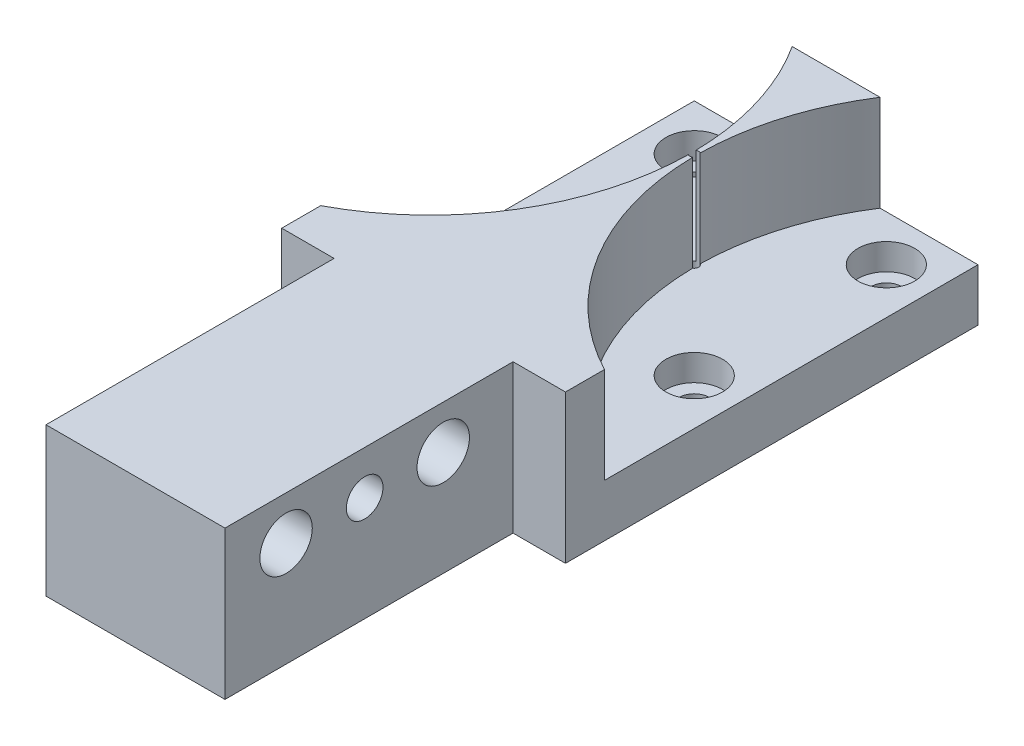
SolidWorks part; units mm, degrees
ref_plane "Front Plane" through (0, 0, 0) normal (0, 0, 1) x (1, 0, 0)
ref_plane "Top Plane" through (0, 0, 0) normal (0, 1, 0) x (1, 0, 0)
ref_plane "Right Plane" through (0, 0, 0) normal (1, 0, 0) x (0, 0, -1)
sketch "Sketch1" plane through (0, 0, 0) normal (0, 1, 0) x (1, 0, 0)
  line L0 (-16.25, 0) -> (16.25, 0)
  line L1 (-16.25, 0) -> (-16.25, -80.25)
  line L2 (-16.25, -80.25) -> (16.25, -80.25)
  line L3 (16.25, -80.25) -> (16.25, 0)
  line L4 (-0.45, -16.25) -> (-0.25, -16.25) construction
  line L5 (0.45, -16.25) -> (0.25, -16.25) construction
  line L6 (-16.25, -52.25) -> (16.25, -52.25) construction
  line L7 (11, -27.25) -> (-11, -27.25) construction
  line L8 (11, -27.25) -> (11, -5.25) construction
  line L9 (11, -5.25) -> (-11, -5.25) construction
  line L10 (-11, -27.25) -> (-11, -5.25) construction
  line L11 (11, -27.25) -> (-11, -5.25) construction
  line L12 (11, -5.25) -> (-11, -27.25) construction
  line L13 (-16.25, -58.25) -> (16.25, -58.25) construction
  line L14 (-16.25, -76.25) -> (16.25, -76.25) construction
  line L15 (-16.25, -70.25) -> (16.25, -70.25) construction
  line L16 (-16.25, -66.75) -> (16.25, -66.75) construction
  line L17 (-16.25, -61.75) -> (16.25, -61.75) construction
  line L18 (0, -52.25) -> (0, -58.25) construction
  line L19 (0, -66.75) -> (0, -61.75) construction
  line L20 (0, -70.25) -> (0, -76.25) construction
  line L21 (0, -58.25) -> (0, -66.75) construction
  line L22 (0, -61.75) -> (0, -70.25) construction
  line L23 (-16.25, -48.25) -> (16.25, -48.25) construction
  line L24 (0, -52.25) -> (0, -48.25) construction
  line L25 (0, -76.25) -> (0, -80.25) construction
  line L26 (0, -16.25) -> (0, 15.25) construction
  line L27 (-12.775, 15.25) -> (12.775, 15.25) construction
  line L28 (-30.25, -46.25) -> (-30.25, -48.25) construction
  arc A0 (-16.25, -42.783) -> (-5.0322, 0) centre (-30.25, -16.25) ccw construction
  circle A1 centre (0, -16.25) radius 0.45 construction
  arc A2 (5.0322, 0) -> (16.25, -42.783) centre (30.25, -16.25) ccw construction
  circle A3 centre (-11, -5.25) radius 5.25 construction
  circle A4 centre (-11, -5.25) radius 3.25 construction
  circle A5 centre (-11, -5.25) radius 1.5 construction
  arc A6 (-16.25, -42.783) -> (-5.0322, 0) centre (-30.25, -16.25) cw construction
  circle A7 centre (-12.775, 15.25) radius 5 construction
  circle A8 centre (12.775, 15.25) radius 5 construction
  point P43 (0, -55.25)
  point P44 (0, -73.25)
  dimension "D1" = 0.9
  dimension "D4" = 2
  dimension "D5" = 6.5
  dimension "D6" = 3
  dimension "D7" = 30
  dimension "D17" = 10
  dimension "D2" = 0.2
  dimension "D3" = 22
  dimension "D8" = 32.5
  dimension "D9" = 4
  dimension "D10" = 6
  dimension "D11" = 18
  dimension "D12" = 5
  dimension "D13" = 2
  dimension "D15" = 31.5
  dimension "D16" = 25.55
  dimension "D18" = 3.5
extrude "Boss-Extrude1" add sketch "Sketch1" against normal blind 6
sketch "Sketch2" plane through (0, 0, 0) normal (0, 1, 0) x (1, 0, 0)
  line L0 (-5.0322, 0) -> (5.0322, 0)
  line L1 (-16.25, -42.783) -> (-16.25, -80.25)
  line L2 (-16.25, -80.25) -> (16.25, -80.25)
  line L3 (16.25, -80.25) -> (16.25, -42.783)
  arc A0 (5.0322, 0) -> (16.25, -42.783) centre (30.25, -16.25) ccw construction
  arc A1 (-16.25, -42.783) -> (-5.0322, 0) centre (-30.25, -16.25) ccw construction
  arc A2 (5.0322, 0) -> (16.25, -42.783) centre (30.25, -16.25) ccw
  arc A3 (-16.25, -42.783) -> (-5.0322, 0) centre (-30.25, -16.25) ccw
extrude "Boss-Extrude2" add sketch "Sketch2" along normal blind 11
sketch "Sketch3" plane through (16.25, 0, 0) normal (1, 0, 0) x (0, 0, -1)
  line L0 (-73.25, 11) -> (-73.25, 1) construction
  line L1 (-80.25, 11) -> (-42.783, 11) construction
  line L3 (-55.25, 11) -> (-55.25, 1) construction
  line L4 (-64.25, 11) -> (-64.25, 1) construction
  line L6 (-80.25, 0) -> (0, 0) construction
  line L7 (-66.75, 0) -> (-61.75, 0) construction
  point P20 (-64.25, 0)
  dimension "D1" = 10
hole_wizard "Ø6.0mm Dowel Hole1" positions "Sketch4" profile "Sketch5" hole size "Ø6.0" standard "ANSI Metric" end condition through all
sketch "Sketch4" plane through (16.25, 0, 0) normal (1, 0, 0) x (0, 0, -1)
  line L0 (-73.25, 11) -> (-73.25, 1) construction
  line L1 (-55.25, 11) -> (-55.25, 1) construction
  point P0 (-73.25, 6)
  point P4 (-55.25, 6)
sketch "Sketch5" plane through (16.25, 6, 73.25) normal (0, 1, 0) x (0, 0, -1)
  line L0 (0, 0) -> (0, 32.5)
  line L1 (0, 32.5) -> (3, 32.5)
  line L2 (3, 32.5) -> (3, 0)
  line L5 (3, 0) -> (0, 0)
  line L11 (0, -6.35) -> (0, 107.95) construction
  dimension "Thru Hole Dia." = 6
  dimension "Thru Hole Depth" = 32.5
hole_wizard "M5x0.8 Tapped Hole1" positions "Sketch6" profile "Sketch7" tap size "M5x0.8" standard "ANSI Metric" end condition through all
sketch "Sketch6" plane through (16.25, 0, 0) normal (1, 0, 0) x (0, 0, -1)
  line L0 (-64.25, 11) -> (-64.25, 1) construction
  point P0 (-64.25, 6)
sketch "Sketch7" plane through (16.25, 6, 64.25) normal (0, 1, 0) x (0, 0, -1)
  line L0 (0, 0) -> (0, 32.5)
  line L1 (0, 32.5) -> (2.1, 32.5)
  line L2 (2.1, 32.5) -> (2.1, 0)
  line L5 (2.1, 0) -> (0, 0)
  line L11 (0, -6.35) -> (0, 107.95) construction
  dimension "Thru Tap Drill Dia." = 4.2
  dimension "Thru Tap Drill Depth" = 32.5
cosmetic thread "Hole Thread1" parameters "D2"=5
hole_wizard "CBORE for M3 SHCS1" positions "Sketch8" profile "Sketch9" counterbore size "M3" standard "ANSI Metric" end condition through all
sketch "Sketch8" plane through (0, 0, 0) normal (0, 1, 0) x (1, 0, 0)
  point P0 (-11, -5.25)
  point P3 (11, -5.25)
  point P6 (11, -27.25)
  point P9 (-11, -27.25)
sketch "Sketch9" plane through (-11, 0, 5.25) normal (1, 0, 0) x (0, 0, 1)
  line L0 (0, 0) -> (0, 6)
  line L1 (0, 6) -> (1.7, 6)
  line L3 (1.7, 6) -> (1.7, 3)
  line L4 (1.7, 3) -> (3.25, 3)
  line L5 (3.25, 3) -> (3.25, 0)
  line L7 (3.25, 0) -> (0, 0)
  line L11 (0, -6.35) -> (0, 107.95) construction
  dimension "Thru Hole Dia." = 3.4
  dimension "Thru Hole Depth" = 6
  dimension "C'Bore Dia." = 6.5
  dimension "C'Bore Depth" = 3
hole_wizard "Ø1.0 (1) Diameter Hole1" positions "Sketch10" profile "Sketch11" hole size "Ø1.0" standard "ANSI Metric" end condition through all
sketch "Sketch10" plane through (0, 11, 0) normal (0, 1, 0) x (1, 0, 0)
  point P0 (0, -16.25)
sketch "Sketch11" plane through (0, 11, 16.25) normal (1, 0, 0) x (0, 0, 1)
  line L0 (0, 0) -> (0, 17)
  line L1 (0, 17) -> (0.5, 17)
  line L2 (0.5, 17) -> (0.5, 0)
  line L5 (0.5, 0) -> (0, 0)
  line L11 (0, -6.35) -> (0, 107.95) construction
  dimension "Thru Hole Dia." = 1
  dimension "Thru Hole Depth" = 17
sketch "Sketch12" plane through (0, -6, 0) normal (0, -1, 0) x (1, 0, 0)
  circle A0 centre (0, 16.25) radius 1.5
  dimension "D1" = 3
extrude "Cut-Extrude1" cut sketch "Sketch12" against normal blind 5
sketch "Sketch13" plane through (0, 11, 0) normal (0, 1, 0) x (1, 0, 0)
  line L0 (-16.25, 0) -> (-16.25, -80.25) construction
  line L1 (-16.25, -47.25) -> (-10.25, -47.25)
  line L2 (-16.25, -47.25) -> (-16.25, -80.25)
  line L3 (-16.25, -80.25) -> (-10.25, -80.25)
  line L4 (-10.25, -47.25) -> (-10.25, -80.25)
  line L5 (-16.25, -80.25) -> (16.25, -80.25) construction
  line L6 (16.25, -80.25) -> (16.25, 0) construction
  line L7 (16.25, -47.25) -> (10.25, -47.25)
  line L8 (16.25, -47.25) -> (16.25, -80.25)
  line L9 (16.25, -80.25) -> (10.25, -80.25)
  line L10 (10.25, -47.25) -> (10.25, -80.25)
  line L11 (-16.25, -48.25) -> (16.25, -48.25) construction
  arc A0 (-16.25, -42.783) -> (-0.2531, -16.6812) centre (-30.25, -16.25) ccw construction
  point P16 (-30.25, -16.25)
  dimension "D1" = 1
  dimension "D2" = 20
extrude "Cut-Extrude2" cut sketch "Sketch13" against normal through all
